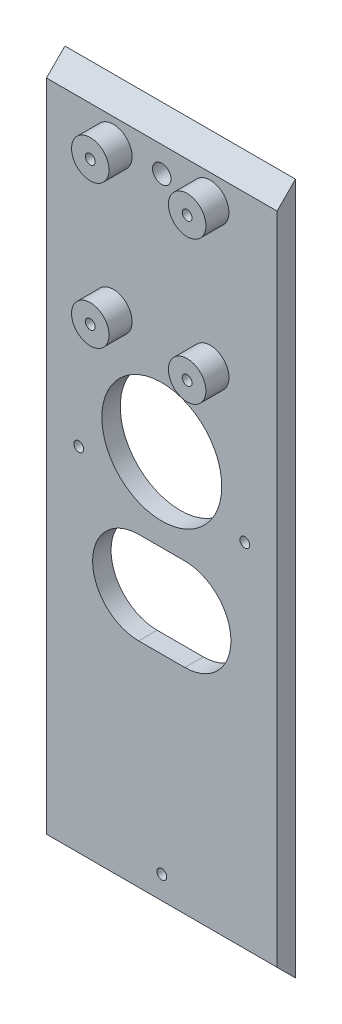
SolidWorks part; units mm, degrees
ref_plane "Front Plane" through (0, 0, 0) normal (1, 0, 0) x (0, 1, 0)
ref_plane "Top Plane" through (0, 0, 0) normal (0, 0, 1) x (0, 1, 0)
ref_plane "Right Plane" through (0, 0, 0) normal (0, 1, 0) x (-1, 0, 0)
sketch "Sketch1" plane through (0, 0, 0) normal (0, 0, 1) x (0, 1, 0)
  line L1 (0, 0) -> (150, 0)
  line L2 (0, 0) -> (0, 50)
  line L3 (0, 50) -> (150, 50)
  line L4 (150, 0) -> (150, 50)
  dimension "D1" = 150
  dimension "D2" = 50
extrude "Boss-Extrude1" add sketch "Sketch1" along normal blind 4
chamfer "Chamfer1" distance 4 angle 45 2 edges at (-25, 150, 4) (-25, 0, 4)
sketch "Sketch2" plane through (0, 0, 4) normal (0, 0, 1) x (1, 0, 0)
  line L0 (0, 4) -> (0, 146) construction
  line L1 (-50, 4) -> (0, 4) construction
  line L2 (-50, 4) -> (-50, 104) construction
  line L3 (-50, 104) -> (0, 104) construction
  line L4 (0, 4) -> (0, 104) construction
  line L5 (-25, 4) -> (-25, 9) construction
  line L6 (-25, 9) -> (-25, 88.3) construction
  line L7 (-50, 104) -> (0, 146) construction
  line L8 (-50, 146) -> (0, 146) construction
  line L9 (-50, 146) -> (-50, 104) construction
  line L10 (-50, 104) -> (0, 104) construction
  line L11 (0, 146) -> (0, 104) construction
  line L12 (-50, 146) -> (0, 104) construction
  line L13 (-25, 9) -> (-25, 70) construction
  line L14 (-30, 60.3) -> (-20, 60.3) construction
  line L15 (-25, 75.3) -> (-25, 60.3) construction
  line L16 (-30, 60.3) -> (-20, 60.3) construction
  line L17 (-30, 70.3) -> (-20, 70.3)
  line L18 (-30, 50.3) -> (-20, 50.3)
  line L19 (-25, 9) -> (-25, 80.3) construction
  line L20 (-43, 80.3) -> (-7, 80.3) construction
  line L21 (-35.5, 140.5) -> (-14.5, 140.5) construction
  line L27 (-38, 107) -> (-12, 107) construction
  line L29 (-38, 107) -> (-38, 143) construction
  line L46 (-25, 9) -> (-25, 44.3) construction
  line L52 (-38, 143) -> (-12, 143) construction
  line L53 (-12, 107) -> (-12, 143) construction
  line L68 (-38, 107) -> (-12, 143) construction
  line L69 (-38, 143) -> (-12, 107) construction
  line L70 (-38, 143) -> (-35.5, 143) construction
  line L71 (-38, 143) -> (-38, 140.5) construction
  line L72 (-38, 140.5) -> (-35.5, 140.5) construction
  line L73 (-35.5, 143) -> (-35.5, 140.5) construction
  line L74 (-12, 143) -> (-14.5, 143) construction
  line L75 (-12, 143) -> (-12, 140.5) construction
  line L76 (-12, 140.5) -> (-14.5, 140.5) construction
  line L77 (-14.5, 143) -> (-14.5, 140.5) construction
  line L78 (-12, 107) -> (-14.5, 107) construction
  line L79 (-12, 107) -> (-12, 109.5) construction
  line L80 (-12, 109.5) -> (-14.5, 109.5) construction
  line L81 (-14.5, 107) -> (-14.5, 109.5) construction
  line L82 (-38, 107) -> (-35.5, 107) construction
  line L83 (-38, 107) -> (-38, 109.5) construction
  line L84 (-38, 109.5) -> (-35.5, 109.5) construction
  line L85 (-35.5, 107) -> (-35.5, 109.5) construction
  circle A0 centre (-25, 88.3) radius 13
  circle A1 centre (-25, 9) radius 1.065
  arc A4 (-30, 70.3) -> (-30, 50.3) centre (-30, 60.3) ccw
  arc A5 (-20, 50.3) -> (-20, 70.3) centre (-20, 60.3) ccw
  circle A8 centre (-7, 80.3) radius 1.065
  circle A9 centre (-43, 80.3) radius 1.065
  circle A13 centre (-25, 44.3) radius 31 construction
  circle A17 centre (-25, 140.5) radius 2
  point P14 (-25, 60.3)
  point P19 (-25, 70)
  point P20 (-25, 60.3)
  point P31 (-25, 80.3)
  point P34 (-25, 125)
  dimension "D6" = 26
  dimension "D7" = 2.13
  dimension "D8" = 15
  dimension "D11" = 10
  dimension "D12" = 71.3
  dimension "D9" = 10
  dimension "D10" = 10
  dimension "D13" = 2.13
  dimension "D14" = 36
  dimension "D15" = 2.13
  dimension "D30" = 62
  dimension "D25" = 2.5
  dimension "D26" = 4
  dimension "D1" = 100
  dimension "D2" = 5
  dimension "D3" = 5
  dimension "D4" = 5
  dimension "D5" = 79.3
  dimension "D16" = 36
  dimension "D17" = 26
  dimension "D18" = 2.5
  dimension "D19" = 2.5
  dimension "D20" = 2.5
  dimension "D21" = 2.5
  dimension "D22" = 2.5
  dimension "D23" = 2.5
  dimension "D24" = 2.5
  dimension "D29" = 35.3
extrude "Cut-Extrude2" cut sketch "Sketch2" against normal blind 4
sketch "Sketch6" plane through (0, 0, 4) normal (0, 0, 1) x (1, 0, 0)
  circle A8 centre (-35.5, 140.5) radius 1.065
  circle A9 centre (-14.5, 140.5) radius 1.065
  circle A10 centre (-14.5, 109.5) radius 1.065
  circle A11 centre (-35.5, 109.5) radius 1.065
  circle A12 centre (-35.5, 140.5) radius 4.065
  circle A13 centre (-14.5, 140.5) radius 4.065
  circle A14 centre (-14.5, 109.5) radius 4.065
  circle A15 centre (-35.5, 109.5) radius 4.065
  dimension "D4" = 2.13
  dimension "D5" = 3
extrude "Boss-Extrude2" add sketch "Sketch6" along normal blind 5
sketch "Sketch8" plane through (0, 0, 0) normal (0, 0, -1) x (1, 0, 0)
  line L5 (-39, -111) -> (-11, -111) construction
  line L7 (-39, -111) -> (-39, -139) construction
  line L8 (-39, -139) -> (-11, -139) construction
  line L9 (-11, -111) -> (-11, -139) construction
  line L10 (-39, -111) -> (-11, -139) construction
  line L11 (-39, -139) -> (-11, -111) construction
  point P0 (-25, -125)
  dimension "D1" = 28
  dimension "D2" = 28
